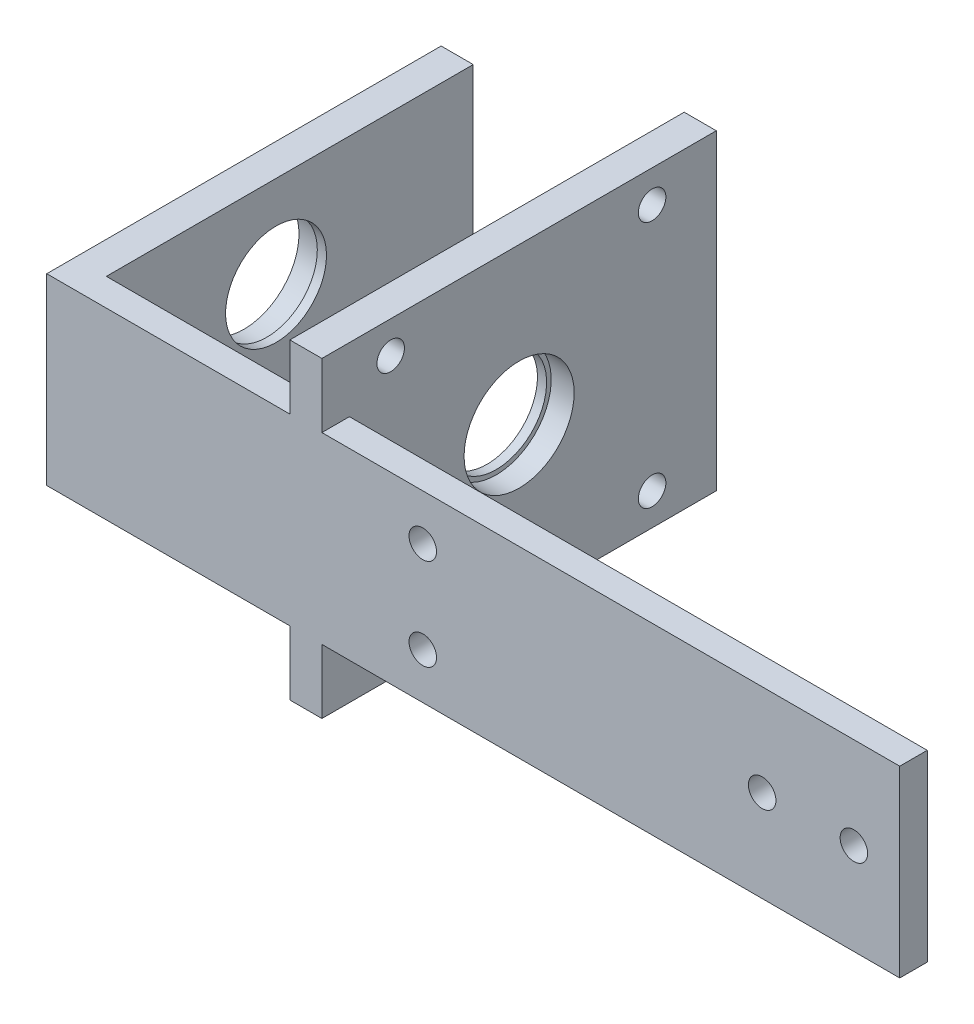
SolidWorks part; units mm, degrees
ref_plane "前视基准面" through (0, 0, 0) normal (0, 0, 1) x (1, 0, 0)
ref_plane "上视基准面" through (0, 0, 0) normal (0, 1, 0) x (1, 0, 0)
ref_plane "右视基准面" through (0, 0, 0) normal (1, 0, 0) x (0, 0, -1)
sketch "草图1" plane through (0, 0, 0) normal (0, 0, 1) x (1, 0, 0)
  line L0 (-10, 9.8542) -> (10, 9.8542)
  line L1 (-10, 9.8542) -> (-10, -10.1458)
  line L2 (10, 9.8542) -> (10, -10.1458)
  line L3 (-10, 9.8542) -> (-53, 9.8542)
  line L4 (-10, -0.1458) -> (10, -0.1458) construction
  line L5 (0, 9.8542) -> (0, -9.8542) construction
  line L6 (-53, -0.1458) -> (-53, 16.8542)
  line L7 (-53, -10.1458) -> (-10, -10.1458)
  line L8 (-53, -0.1458) -> (-53, -17.1458)
  line L9 (-53, -17.1458) -> (-56.5, -17.1458)
  line L10 (-56.5, 16.8542) -> (-56.5, 9.8542)
  line L11 (-53, 16.8542) -> (-56.5, 16.8542)
  line L12 (-56.5, 9.8542) -> (-79.5, 9.8542)
  line L13 (-10, -10.1458) -> (10, -10.1458)
  line L14 (-79.5, -10.1458) -> (-56.5, -10.1458)
  line L15 (-79.5, 9.8542) -> (-79.5, -10.1458)
  line L16 (-79.5, -10.1458) -> (-83, -10.1458)
  line L17 (-83, -10.1458) -> (-83, 9.8542)
  line L18 (-83, 9.8542) -> (-79.5, 9.8542)
  line L19 (-56.5, -10.1458) -> (-56.5, -17.1458)
  line L20 (-56.5, 9.8542) -> (-56.5, -10.1458)
  circle A2 centre (-5, -0.1458) radius 1.5
  circle A3 centre (5, -0.1458) radius 1.5
extrude "凸台-拉伸1" add sketch "草图1" along normal blind 3 contours L6 L8 L7 L1 L3 | L1 L13 L2 L0 | L6 L11 L9 L8 | L12 L14 | L18 L17 L16 region at (0, -0.1458, 0) region at (-31.5, -0.1458, 0) region at (-54.75, -0.1458, 0) region at (-68, -0.1458, 0) region at (-81.25, -0.1458, 0)
extrude "凸台-拉伸2" add sketch "草图1<3>" against normal blind 40 contours L10 L20 L19 L9 L8 L6 L11
sketch "草图1<3>" plane through (0, 0, 0) normal (0, 0, 1) x (1, 0, 0) same geometry as "草图1"
sketch "草图2" plane through (-53, 0, 0) normal (-1, 0, 0) x (0, 0, -1)
  line L0 (-3, 0.1458) -> (40, 0.1458) construction
  line L1 (18.75, 17.1458) -> (18.75, -16.8542) construction
  circle A0 centre (33, -13.3542) radius 1.5
  circle A1 centre (4.5, 13.6458) radius 1.5
  circle A2 centre (33, 13.6458) radius 1.5
  circle A12 centre (4.5, -13.3542) radius 1.5
extrude "切除-拉伸1" cut sketch "草图2" against normal mid plane 20
extrude "凸台-拉伸3" add sketch "草图1<4>" against normal blind 40 contours L18 L17 L16 region at (-81.25, -0.1458, 0)
sketch "草图1<4>" plane through (0, 0, 0) normal (0, 0, 1) x (1, 0, 0) same geometry as "草图1"
sketch "草图3" plane through (-83, 0, 0) normal (-1, 0, 0) x (0, 0, 1)
  circle A0 centre (-18.5, -0.1458) radius 6
extrude "切除-拉伸2" cut sketch "草图3" against normal blind 38 contours A0 region at (-83, -0.1458, -18.5)
sketch "草图4" plane through (-56.5, 0, 0) normal (-1, 0, 0) x (0, 0, 1)
  circle A0 centre (-18.5, -0.1458) radius 6
  circle A1 centre (-18.5, -0.1458) radius 5.5
extrude "凸台-拉伸4" add sketch "草图4" against normal blind 1
ref_plane "基准面1" through (-68, 0, 0) normal (1, 0, 0) x (0, 0, -1)
sketch "草图5" plane through (-79.5, 0, 0) normal (1, 0, 0) x (0, 0, -1)
  circle A0 centre (18.5, -0.1458) radius 6
  circle A1 centre (18.5, -0.1458) radius 5.5
extrude "凸台-拉伸5" add sketch "草图5" against normal blind 1
sketch "草图7" plane through (0, 0, 3) normal (0, 0, 1) x (1, 0, 0)
  line L0 (-49.5, -10.1461) -> (-49.5, 10.8539)
  line L1 (-34.5, -10.1461) -> (-34.5, 10.8539)
  line L2 (-49.5, 10.8539) -> (-34.5, 10.8539)
  line L3 (-49.5, -10.1461) -> (-34.5, -10.1461)
  line L31 (10, -10.1461) -> (10, 9.8539)
  circle A4 centre (-42, -5.1461) radius 1.5
  circle A6 centre (-42, 4.8539) radius 1.5
extrude "切除-拉伸4" cut sketch "草图7" against normal blind 5 contours A6 | A4 region at (-42, -5.1461, 3) region at (-42, 4.8539, 3)
